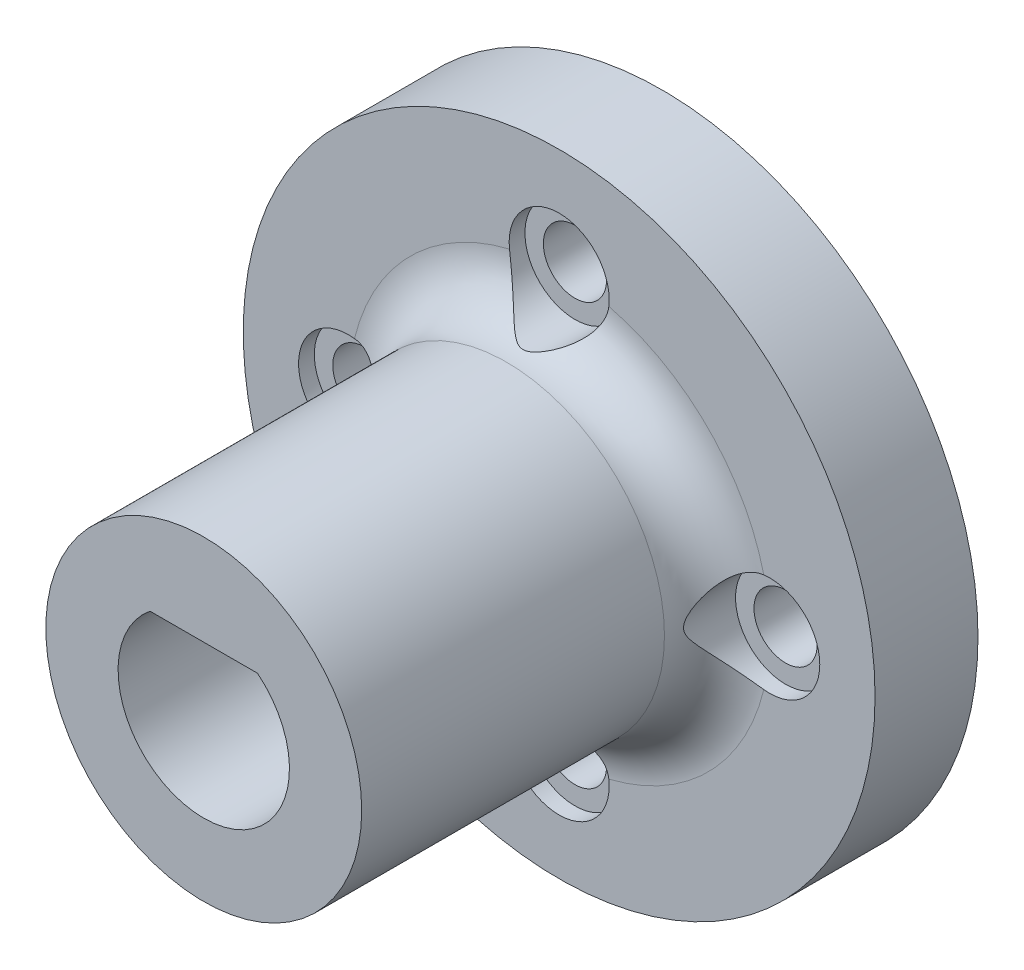
SolidWorks part; units mm, degrees
ref_plane "Plan de face" through (0, 0, 0) normal (0, 0, 1) x (1, 0, 0)
ref_plane "Plan de dessus" through (0, 0, 0) normal (0, 1, 0) x (1, 0, 0)
ref_plane "Plan de droite" through (0, 0, 0) normal (1, 0, 0) x (0, 0, -1)
sketch "Esquisse1" plane through (0, 0, 0) normal (0, 0, 1) x (1, 0, 0)
  circle A0 centre (0, 0) radius 12
  dimension "D1" = 24
extrude "Boss.-Extru.1" add sketch "Esquisse1" along normal blind 3.91
sketch "Esquisse6" plane through (0, 0, 0) normal (0, 0, -1) x (-1, 0, 0)
  circle A0 centre (0, 0) radius 4.15
  dimension "D1" = 8.3
extrude "Enlèv. mat.-Extru.2" cut sketch "Esquisse6" against normal blind 2.5
sketch "Esquisse7" plane through (0, 0, 3.91) normal (0, 0, 1) x (1, 0, 0)
  line L0 (2.0418, 2.535) -> (-2.0418, 2.535)
  line L1 (-5.4714, -3.255) -> (6.192, -3.255) construction
  arc A0 (-2.0418, 2.535) -> (2.0418, 2.535) centre (0, 0) ccw
  circle A1 centre (0, 0) radius 6
  dimension "D1" = 6.51
  dimension "D3" = 12
  dimension "D2" = 5.79
extrude "Boss.-Extru.2" add sketch "Esquisse7" along normal blind 13.5 contours A1 L1 A0 L0 | L1 A1 region at (-2.5202, -3.1035, 3.91) region at (0, -4.3779, 3.91)
hole_wizard "Chambrage pour vis à tête ronde bombée M21" positions "Esquisse10" profile "Esquisse11" counterbore size "M2" standard "Ansi Metric" end condition through all
sketch "Esquisse10" plane through (0, 0, 3.91) normal (0, 0, 1) x (1, 0, 0)
  point P0 (0, 8)
  dimension "D1" = 8
sketch "Esquisse11" plane through (0, 8, 3.91) normal (1, 0, 0) x (0, -1, 0)
  line L0 (0, 0) -> (0, 3.91)
  line L1 (0, 3.91) -> (1.2, 3.91)
  line L3 (1.2, 3.91) -> (1.2, 0.6)
  line L4 (1.2, 0.6) -> (1.9, 0.6)
  line L5 (1.9, 0.6) -> (1.9, 0)
  line L7 (1.9, 0) -> (0, 0)
  line L11 (0, -6.35) -> (0, 107.95) construction
  dimension "Diamètre du perçage jusqu'au prochain" = 2.4
  dimension "Profondeur du perçage jusqu'au prochain" = 3.91
  dimension "Diamètre du chambrage" = 3.8
  dimension "Profondeur du chambrage" = 0.6
pattern_circular "Répétition circulaire2" count 4 every 90 about axis through (0, 0, 3.91) along (0, 0, 1) of "Chambrage pour vis à tête ronde bombée M21"
fillet "Congé1" radius 2 1 edges at (6, 0, 3.91)
